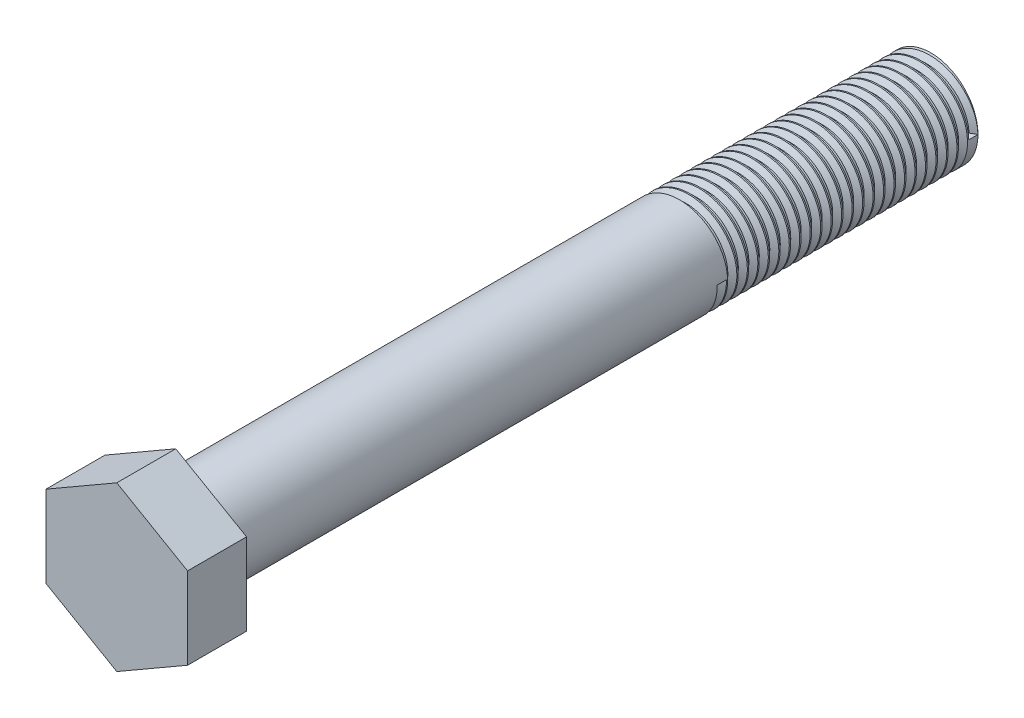
SolidWorks part; units mm, degrees
ref_plane "Front Plane" through (0, 0, 0) normal (0, 0, 1) x (1, 0, 0)
ref_plane "Top Plane" through (0, 0, 0) normal (0, 1, 0) x (1, 0, 0)
ref_plane "Right Plane" through (0, 0, 0) normal (1, 0, 0) x (0, 0, -1)
sketch "Sketch1" plane through (0, 0, 0) normal (0, 0, 1) x (1, 0, 0)
  line L0 (15.4227, 0) -> (-15.4227, 0) construction
  line L1 (0, -14.249) -> (0, 14.249) construction
  circle A0 centre (0, 0) radius 4.7625
  point P6 (0, 0)
  point P9 (0, 0)
  dimension "D1" = 9.525
extrude "Boss-Extrude1" add sketch "Sketch1" along normal mid plane 76.2
sketch "Sketch2" plane through (0, 0, 38.1) normal (0, 0, 1) x (1, 0, 0)
  line L0 (-16.1082, 0) -> (16.1082, 0) construction
  line L1 (0, -11.9485) -> (0, 11.9485) construction
  line L3 (0, 8.2489) -> (-7.1438, 4.1244)
  line L4 (-7.1438, 4.1244) -> (-7.1438, -4.1244)
  line L5 (-7.1438, -4.1244) -> (0, -8.2489)
  line L6 (0, -8.2489) -> (7.1437, -4.1244)
  line L7 (7.1437, -4.1244) -> (7.1437, 4.1244)
  line L8 (7.1437, 4.1244) -> (0, 8.2489)
  circle A0 centre (0, 0) radius 7.1438 construction
  point P4 (0, 0)
  point P8 (0, 0)
  dimension "D1" = 14.2875
extrude "Boss-Extrude2" add sketch "Sketch2" along normal blind 5.9531
thread "Thread2" pitch 1.0583 method cut profile "Thread Profile2" start angle 0, offset 0, length 25.4, pitch 1.0583, diameter 9.525
ref_plane "Plane2" through (4.7625, 0, -38.1) normal (0, -1, 0) x (1, 0, 0)
sketch "Thread Profile2" plane through (4.7625, 0, -38.1) normal (0, -1, 0) x (1, 0, 0)
  line L0 (0, 0) -> (0, 1.0583) construction
  line L11 (0, 0) -> (0, 0.926)
  line L12 (0, 0.926) -> (-0.5728, 0.5953)
  line L13 (-0.5728, 0.5953) -> (-0.5728, 0.3307)
  line L15 (-0.5728, 0.3307) -> (0, 0)
  line L17 (-0.5728, 0.463) -> (0, 0.463) construction
  point P2 (0, 0)
  dimension "Pitch" = 1.0583
  dimension "Profile_Angle" = 60
  dimension "Profile_Land" = 0.2646
  dimension "Profile_Height" = 0.5728
